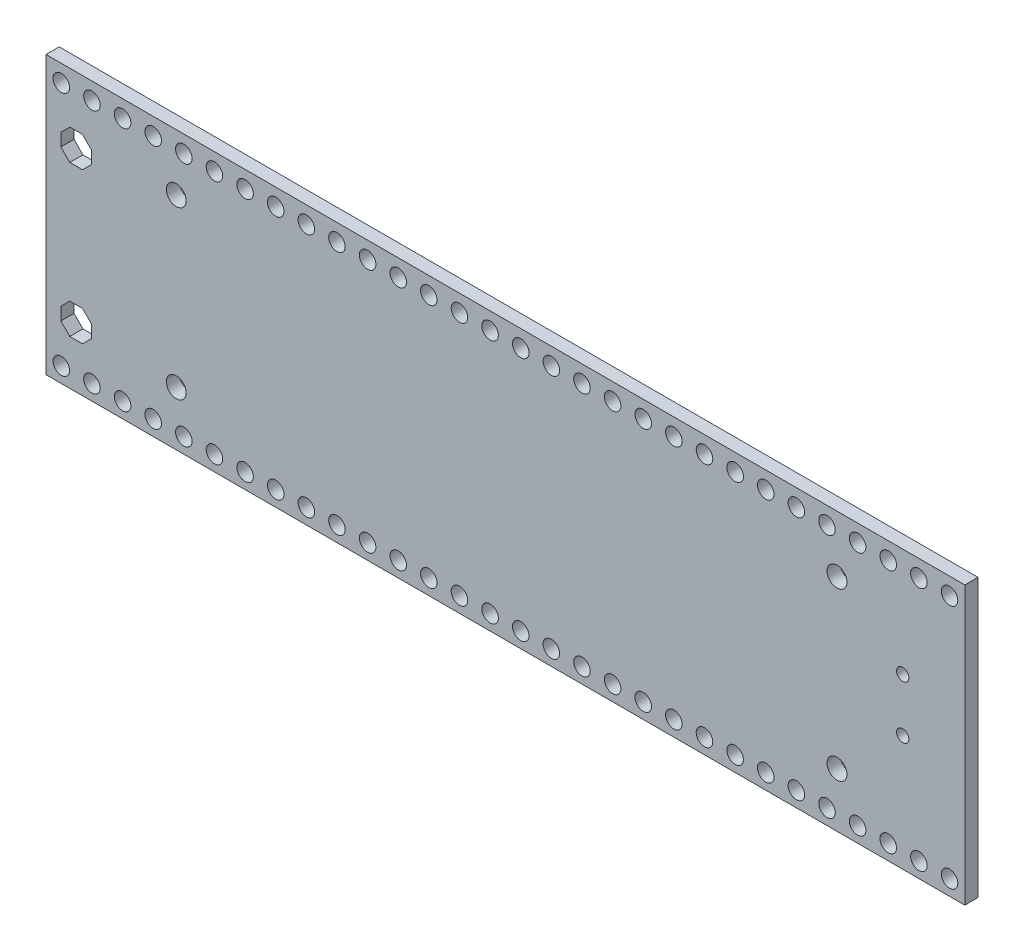
SolidWorks part; units mm, degrees
ref_plane "Front Plane" through (0, 0, 0) normal (0, 0, 1) x (1, 0, 0)
ref_plane "Top Plane" through (0, 0, 0) normal (0, 1, 0) x (1, 0, 0)
ref_plane "Right Plane" through (0, 0, 0) normal (1, 0, 0) x (0, 0, -1)
sketch "Sketch1" plane through (0, 0, 0) normal (0, 0, 1) x (1, 0, 0)
  line L8 (0, 23) -> (0, 0)
  line L9 (0, 0) -> (76.2, 0)
  line L10 (76.2, 0) -> (76.2, 23)
  line L11 (76.2, 23) -> (0, 23)
  line L28 (3.77, 16.9739) -> (3.77, 18.026)
  line L29 (3.026, 16.23) -> (3.77, 16.9739)
  line L30 (1.9739, 16.23) -> (3.026, 16.23)
  line L31 (1.23, 16.9739) -> (1.9739, 16.23)
  line L32 (1.23, 18.026) -> (1.23, 16.9739)
  line L33 (1.9739, 18.77) -> (1.23, 18.026)
  line L34 (3.026, 18.77) -> (1.9739, 18.77)
  line L35 (3.77, 18.026) -> (3.026, 18.77)
  line L44 (3.77, 4.4739) -> (3.77, 5.526)
  line L45 (3.026, 3.73) -> (3.77, 4.4739)
  line L46 (1.9739, 3.73) -> (3.026, 3.73)
  line L47 (1.23, 4.4739) -> (1.9739, 3.73)
  line L48 (1.23, 5.526) -> (1.23, 4.4739)
  line L49 (1.9739, 6.27) -> (1.23, 5.526)
  line L50 (3.026, 6.27) -> (1.9739, 6.27)
  line L51 (3.77, 5.526) -> (3.026, 6.27)
  circle A2 centre (1.27, 21.59) radius 0.6858
  circle A4 centre (3.81, 21.59) radius 0.6858
  circle A6 centre (6.35, 21.59) radius 0.6858
  circle A8 centre (8.89, 21.59) radius 0.6858
  circle A10 centre (11.43, 21.59) radius 0.6858
  circle A12 centre (13.97, 21.59) radius 0.6858
  circle A14 centre (16.51, 21.59) radius 0.6858
  circle A16 centre (19.05, 21.59) radius 0.6858
  circle A18 centre (21.59, 21.59) radius 0.6858
  circle A20 centre (24.13, 21.59) radius 0.6858
  circle A22 centre (26.67, 21.59) radius 0.6858
  circle A24 centre (29.21, 21.59) radius 0.6858
  circle A26 centre (31.75, 21.59) radius 0.6858
  circle A28 centre (34.29, 21.59) radius 0.6858
  circle A30 centre (36.83, 21.59) radius 0.6858
  circle A32 centre (39.37, 21.59) radius 0.6858
  circle A34 centre (41.91, 21.59) radius 0.6858
  circle A36 centre (44.45, 21.59) radius 0.6858
  circle A38 centre (46.99, 21.59) radius 0.6858
  circle A40 centre (49.53, 21.59) radius 0.6858
  circle A42 centre (52.07, 21.59) radius 0.6858
  circle A44 centre (54.61, 21.59) radius 0.6858
  circle A46 centre (57.15, 21.59) radius 0.6858
  circle A48 centre (59.69, 21.59) radius 0.6858
  circle A50 centre (62.23, 21.59) radius 0.6858
  circle A52 centre (64.77, 21.59) radius 0.6858
  circle A54 centre (67.31, 21.59) radius 0.6858
  circle A56 centre (69.85, 21.59) radius 0.6858
  circle A58 centre (72.39, 21.59) radius 0.6858
  circle A60 centre (74.93, 21.59) radius 0.6858
  circle A62 centre (65.6, 18.3) radius 0.825
  circle A64 centre (65.6, 4.5) radius 0.825
  circle A66 centre (10.8, 18.3) radius 0.825
  circle A68 centre (10.8, 4.5) radius 0.825
  circle A70 centre (71.05, 14) radius 0.508
  circle A72 centre (71.05, 9.6) radius 0.508
  circle A74 centre (1.27, 1.27) radius 0.6858
  circle A76 centre (3.81, 1.27) radius 0.6858
  circle A78 centre (6.35, 1.27) radius 0.6858
  circle A80 centre (8.89, 1.27) radius 0.6858
  circle A82 centre (11.43, 1.27) radius 0.6858
  circle A84 centre (13.97, 1.27) radius 0.6858
  circle A86 centre (16.51, 1.27) radius 0.6858
  circle A88 centre (19.05, 1.27) radius 0.6858
  circle A90 centre (21.59, 1.27) radius 0.6858
  circle A92 centre (24.13, 1.27) radius 0.6858
  circle A94 centre (26.67, 1.27) radius 0.6858
  circle A96 centre (29.21, 1.27) radius 0.6858
  circle A98 centre (31.75, 1.27) radius 0.6858
  circle A100 centre (34.29, 1.27) radius 0.6858
  circle A102 centre (36.83, 1.27) radius 0.6858
  circle A104 centre (39.37, 1.27) radius 0.6858
  circle A106 centre (41.91, 1.27) radius 0.6858
  circle A108 centre (44.45, 1.27) radius 0.6858
  circle A110 centre (46.99, 1.27) radius 0.6858
  circle A112 centre (49.53, 1.27) radius 0.6858
  circle A114 centre (52.07, 1.27) radius 0.6858
  circle A116 centre (54.61, 1.27) radius 0.6858
  circle A118 centre (59.69, 1.27) radius 0.6858
  circle A120 centre (57.15, 1.27) radius 0.6858
  circle A122 centre (62.23, 1.27) radius 0.6858
  circle A124 centre (64.77, 1.27) radius 0.6858
  circle A126 centre (69.85, 1.27) radius 0.6858
  circle A128 centre (67.31, 1.27) radius 0.6858
  circle A130 centre (72.39, 1.27) radius 0.6858
  circle A132 centre (74.93, 1.27) radius 0.6858
extrude "Main board" add sketch "Sketch1" along normal blind 0.5461 and the other way blind 0.5461
sketch "Sketch2" plane through (0, 0, -0.5461) normal (0, 0, -1) x (-1, 0, 0)
  line L0 (-76.2, 0) -> (-76.2, 23) construction
  line L1 (-69.9008, 14.0338) -> (-64.9478, 14.0338)
  line L2 (-69.9008, 14.0338) -> (-69.9008, 9.0808)
  line L3 (-69.9008, 9.0808) -> (-64.9478, 9.0808)
  line L4 (-64.9478, 14.0338) -> (-64.9478, 9.0808)
  line L5 (-76.2, 23) -> (0, 23) construction
  line L6 (-62.484, 17.2342) -> (-57.531, 17.2342)
  line L7 (-62.484, 17.2342) -> (-62.484, 12.2812)
  line L8 (-62.484, 12.2812) -> (-57.531, 12.2812)
  line L9 (-57.531, 17.2342) -> (-57.531, 12.2812)
  line L10 (-62.484, 9.906) -> (-57.531, 9.906)
  line L11 (-62.484, 9.906) -> (-62.484, 4.953)
  line L12 (-62.484, 4.953) -> (-57.531, 4.953)
  line L13 (-57.531, 9.906) -> (-57.531, 4.953)
  line L14 (0, 0) -> (-76.2, 0) construction
  dimension "D1" = 4.953
  dimension "D2" = 11.2522
  dimension "D3" = 13.9192
  dimension "D4" = 18.669
  dimension "D5" = 10.7188
  dimension "D6" = 9.906
extrude "Buttons on back" add sketch "Sketch2" along normal blind 1.397
sketch "Sketch3" plane through (0, 0, -0.5461) normal (0, 0, -1) x (-1, 0, 0)
  line L0 (-76.2, 23) -> (0, 23) construction
  line L1 (-30.734, 17.7676) -> (-25.2476, 17.7676)
  line L2 (-30.734, 17.7676) -> (-30.734, 8.014)
  line L3 (-30.734, 8.014) -> (-25.2476, 8.014)
  line L4 (-25.2476, 17.7676) -> (-25.2476, 8.014)
  line L5 (0, 23) -> (0, 0) construction
  dimension "D1" = 9.7536
  dimension "D2" = 5.4864
  dimension "D3" = 14.986
  dimension "D4" = 30.734
extrude "Chip on back" add sketch "Sketch3" along normal blind 0.9398
